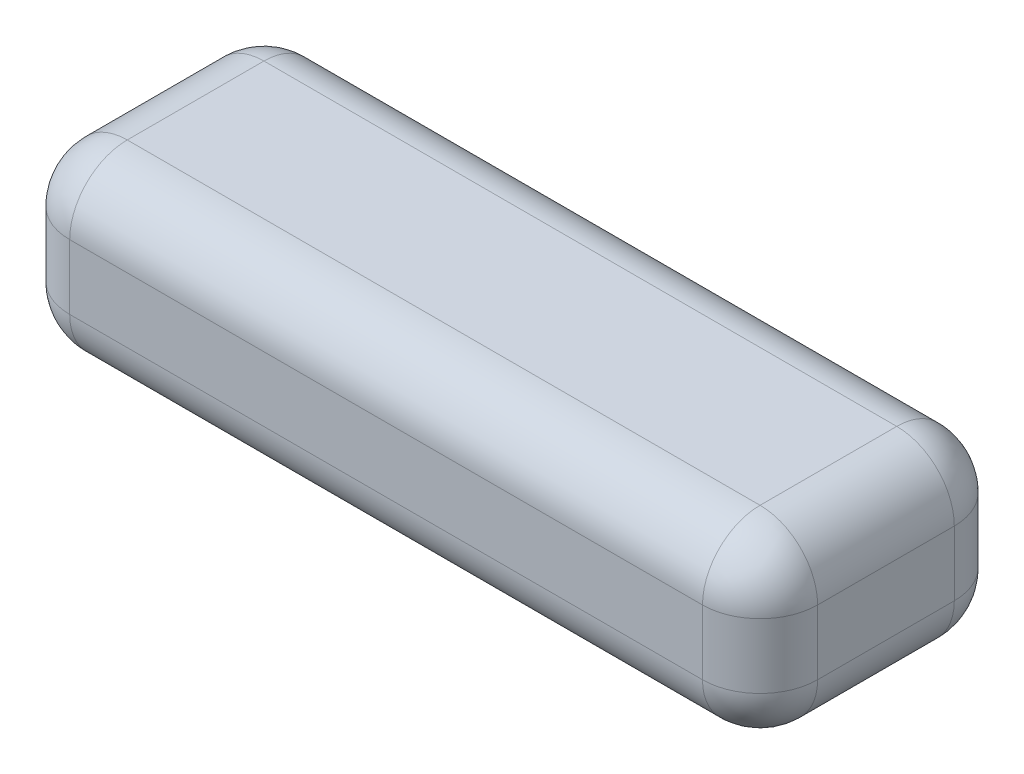
SolidWorks part; units mm, degrees
ref_plane "Front Plane" through (0, 0, 0) normal (0, 0, 1) x (1, 0, 0)
ref_plane "Top Plane" through (0, 0, 0) normal (0, 1, 0) x (1, 0, 0)
ref_plane "Right Plane" through (0, 0, 0) normal (1, 0, 0) x (0, 0, -1)
sketch "Sketch1" plane through (0, 0, 0) normal (0, 1, 0) x (1, 0, 0)
  line L1 (-51.975, 17.5) -> (51.975, 17.5)
  line L2 (-51.975, 17.5) -> (-51.975, -17.5)
  line L3 (-51.975, -17.5) -> (51.975, -17.5)
  line L4 (51.975, 17.5) -> (51.975, -17.5)
  line L5 (-51.975, 17.5) -> (51.975, -17.5) construction
  line L6 (-51.975, -17.5) -> (51.975, 17.5) construction
  point P0 (0, 0)
  dimension "D1" = 35
  dimension "D2" = 103.95
extrude "Boss-Extrude1" add sketch "Sketch1" along normal blind 25
fillet "Fillet1" radius 8 12 edges at (-51.975, 0, 0) (51.975, 0, 0) (51.975, 12.5, -17.5) (-51.975, 12.5, -17.5) (0, 0, -17.5) (-51.975, 12.5, 17.5) (51.975, 12.5, 17.5) (0, 0, 17.5) (0, 25, 17.5) (-51.975, 25, 0) (0, 25, -17.5) (51.975, 25, 0)
